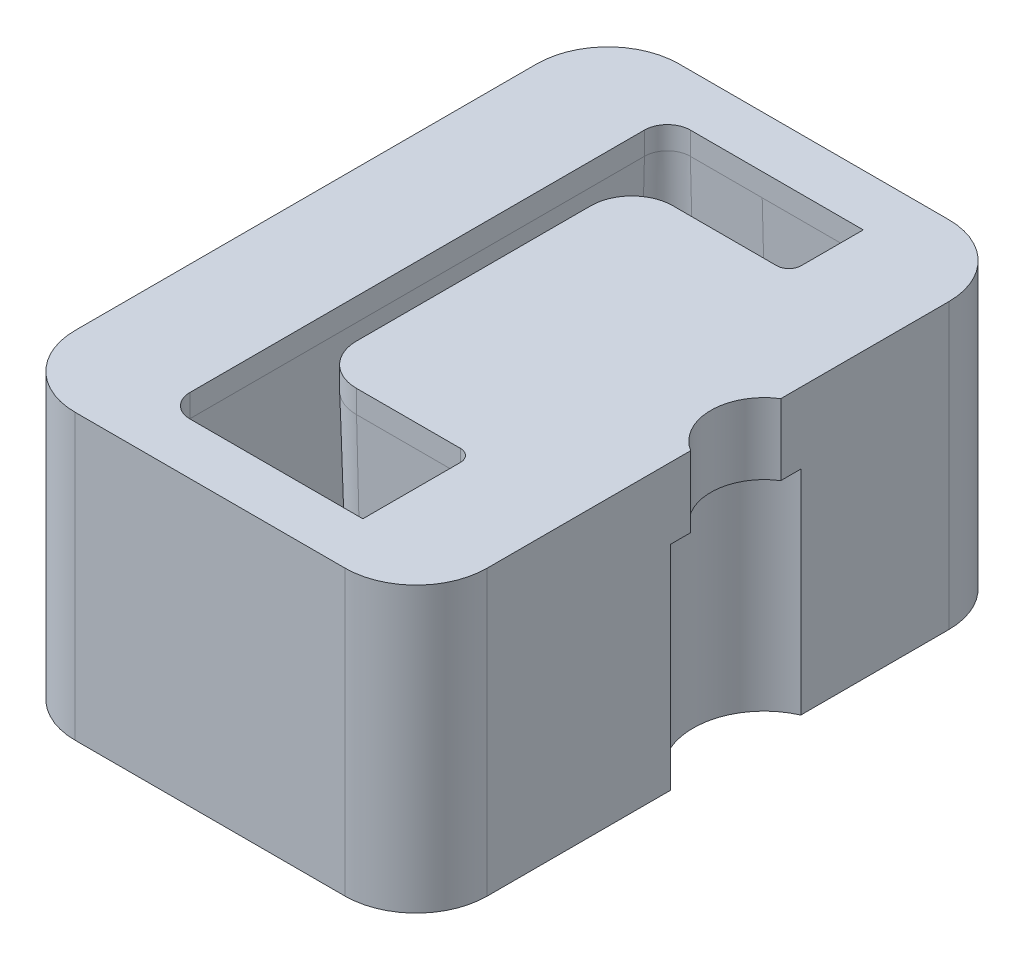
SolidWorks part; units mm, degrees
material "K110"
ref_plane "Front Plane" through (0, 0, 0) normal (0, 0, 1) x (1, 0, 0)
ref_plane "Top Plane" through (0, 0, 0) normal (0, 1, 0) x (1, 0, 0)
ref_plane "Right Plane" through (0, 0, 0) normal (1, 0, 0) x (0, 0, -1)
sketch "Sketch1" plane through (0, 0, 0) normal (0, 1, 0) x (1, 0, 0)
  line L1 (-29, -42.5) -> (29, -42.5)
  line L2 (-29, -42.5) -> (-29, 42.5)
  line L3 (-29, 42.5) -> (29, 42.5)
  line L4 (29, -42.5) -> (29, 42.5)
  line L5 (-29, -42.5) -> (29, 42.5) construction
  line L6 (-29, 42.5) -> (29, -42.5) construction
  point P0 (0, 0)
  dimension "D1" = 85
  dimension "D2" = 58
extrude "Boss-Extrude1" add sketch "Sketch1" against normal blind 40
fillet "Fillet1" radius 10 4 edges at (-29, -20, -42.5) (29, -20, -42.5) (29, -20, 42.5) (-29, -20, 42.5)
sketch "Sketch2" plane through (0, 0, 0) normal (0, 1, 0) x (1, 0, 0)
  line L16 (14.23, 35.23) -> (-10.12, 35.23)
  line L17 (-13.35, 32) -> (-13.35, -32)
  line L18 (-10.12, -35.23) -> (14.23, -35.23)
  line L19 (14.23, -35.23) -> (14.23, -21.5)
  line L20 (12.5, -19.77) -> (-2.12, -19.77)
  line L21 (-7.89, -14) -> (-7.89, 19)
  line L22 (-2.12, 24.77) -> (12.5, 24.77)
  line L23 (14.23, 26.5) -> (14.23, 35.23)
  line L24 (14.23, 35.23) -> (-10.12, 35.23)
  line L25 (-13.35, 32) -> (-13.35, -32)
  line L26 (-10.12, -35.23) -> (14.23, -35.23)
  line L27 (14.23, -35.23) -> (14.23, -21.5)
  line L28 (12.5, -19.77) -> (-2.12, -19.77)
  line L29 (-7.89, -14) -> (-7.89, 19)
  line L30 (-2.12, 24.77) -> (12.5, 24.77)
  line L31 (14.23, 26.5) -> (14.23, 35.23)
  arc A12 (-10.12, 35.23) -> (-13.35, 32) centre (-10.12, 32) ccw
  arc A13 (-13.35, -32) -> (-10.12, -35.23) centre (-10.12, -32) ccw
  arc A14 (14.23, -21.5) -> (12.5, -19.77) centre (12.5, -21.5) ccw
  arc A15 (-7.89, -14) -> (-2.12, -19.77) centre (-2.12, -14) ccw
  arc A16 (-2.12, 24.77) -> (-7.89, 19) centre (-2.12, 19) ccw
  arc A17 (12.5, 24.77) -> (14.23, 26.5) centre (12.5, 26.5) ccw
  arc A18 (-10.12, 35.23) -> (-13.35, 32) centre (-10.12, 32) ccw
  arc A19 (-13.35, -32) -> (-10.12, -35.23) centre (-10.12, -32) ccw
  arc A20 (14.23, -21.5) -> (12.5, -19.77) centre (12.5, -21.5) ccw
  arc A21 (-7.89, -14) -> (-2.12, -19.77) centre (-2.12, -14) ccw
  arc A22 (-2.12, 24.77) -> (-7.89, 19) centre (-2.12, 19) ccw
  arc A23 (12.5, 24.77) -> (14.23, 26.5) centre (12.5, 26.5) ccw
  dimension "D1" = 0.23
extrude "Cut-Extrude1" cut sketch "Sketch2" against normal up to next
sketch "Sketch3" plane through (0, 0, 0) normal (1, 0, 0) x (0, 0, -1)
  line L0 (35.23, -3.2) -> (36.1936, -40)
  line L1 (35.23, -40) -> (35.23, 0) construction
  line L2 (32.5, -40) -> (42.5, -40) construction
  line L3 (36.1936, -40) -> (35.23, -40)
  line L4 (35.23, -40) -> (35.23, -3.2)
  line L5 (31.9, 0) -> (-31.9, 0) construction
  dimension "D1" = 3.2
  dimension "D2" = 1.5
sketch "Sketch5" plane through (0, 0, 0) normal (0, 1, 0) x (1, 0, 0)
  line L0 (12.5, -19.77) -> (-2.12, -19.77) construction
  line L1 (14.23, -35.23) -> (14.23, -21.5) construction
  line L2 (-10.12, -35.23) -> (14.23, -35.23) construction
  line L3 (-7.89, -14) -> (-7.89, 19) construction
  line L4 (-2.12, 24.77) -> (12.5, 24.77) construction
  line L5 (-13.35, 32) -> (-13.35, -32) construction
  line L6 (14.23, 35.23) -> (-10.12, 35.23) construction
  line L7 (14.23, 26.5) -> (14.23, 35.23) construction
  line L8 (12.5, -19.77) -> (-2.12, -19.77)
  line L9 (14.23, -35.23) -> (14.23, -21.5)
  line L10 (-10.12, -35.23) -> (14.23, -35.23)
  line L11 (-7.89, -14) -> (-7.89, 19)
  line L12 (-2.12, 24.77) -> (12.5, 24.77)
  line L13 (-13.35, 32) -> (-13.35, -32)
  line L14 (14.23, 35.23) -> (-10.12, 35.23)
  line L15 (14.23, 26.5) -> (14.23, 35.23)
  arc A0 (-7.89, -14) -> (-2.12, -19.77) centre (-2.12, -14) ccw construction
  arc A1 (14.23, -21.5) -> (12.5, -19.77) centre (12.5, -21.5) ccw construction
  arc A2 (-13.35, -32) -> (-10.12, -35.23) centre (-10.12, -32) ccw construction
  arc A3 (-2.12, 24.77) -> (-7.89, 19) centre (-2.12, 19) ccw construction
  arc A4 (-10.12, 35.23) -> (-13.35, 32) centre (-10.12, 32) ccw construction
  arc A5 (12.5, 24.77) -> (14.23, 26.5) centre (12.5, 26.5) ccw construction
  arc A6 (-7.89, -14) -> (-2.12, -19.77) centre (-2.12, -14) ccw
  arc A7 (14.23, -21.5) -> (12.5, -19.77) centre (12.5, -21.5) ccw
  arc A8 (-13.35, -32) -> (-10.12, -35.23) centre (-10.12, -32) ccw
  arc A9 (-2.12, 24.77) -> (-7.89, 19) centre (-2.12, 19) ccw
  arc A10 (-10.12, 35.23) -> (-13.35, 32) centre (-10.12, 32) ccw
  arc A11 (12.5, 24.77) -> (14.23, 26.5) centre (12.5, 26.5) ccw
sweep "Cut-Sweep1" cut profiles "Sketch3" path "Sketch5"
hole_wizard "M6 Tapped Hole1" positions "Sketch8" profile "Sketch7" tap size "M6" standard "ISO"
sketch "Sketch8" plane through (0, -40, 0) normal (0, -1, 0) x (-1, 0, 0)
  line L0 (-19, 42.5) -> (19, 42.5) construction
  line L1 (-29, -32.5) -> (-29, 32.5) construction
  line L2 (29, 32.5) -> (29, -32.5) construction
  line L3 (19, -42.5) -> (-19, -42.5) construction
  point P0 (-22, 35.5)
  point P2 (22, 35.5)
  point P4 (22, -35.5)
  point P6 (-22, -35.5)
  dimension "D1" = 7
  dimension "D2" = 7
  dimension "D3" = 7
  dimension "D4" = 7
sketch "Sketch7" plane through (22, -40, -35.5) normal (1, 0, 0) x (0, 0, -1)
  line L0 (0, 0) -> (0, 18.5022)
  line L1 (0, 18.5022) -> (2.5, 17)
  line L2 (2.5, 17) -> (2.5, 0.525)
  line L3 (2.5, 0.525) -> (3.025, 0)
  line L5 (3.025, 0) -> (0, 0)
  line L6 (-2.5, 0.525) -> (-3.025, 0) construction
  line L10 (0, 18.5022) -> (-2.5, 17) construction
  line L11 (0, -6.35) -> (0, 107.95) construction
  dimension "Tap Drill Dia." = 5
  dimension "Tap Drill Depth" = 17
  dimension "Near C'Sink Dia." = 6.05
  dimension "Near C'Sink Angle" = 90
  dimension "Drill Angle" = 118
cosmetic thread "Hole Thread1" parameters "D1"=12, "D2"=6
cosmetic thread "Hole Thread2" parameters "D1"=12, "D2"=6
cosmetic thread "Hole Thread3" parameters "D1"=12, "D2"=6
cosmetic thread "Hole Thread4" parameters "D1"=12, "D2"=6
extrude "Cut-Extrude2" cut sketch "Sketch9" against normal through all
sketch "Sketch9" plane through (296.88, 0, 7.73) normal (0, 1, 0) x (1, 0, 0)
  circle A0 centre (-263.88, 10.23) radius 7.5
extrude "Cut-Extrude3" cut sketch "Sketch10" against normal blind 30
sketch "Sketch10" plane through (296.88, -40, 7.73) normal (0, -1, 0) x (1, 0, 0)
  circle A0 centre (-263.88, -10.23) radius 10
